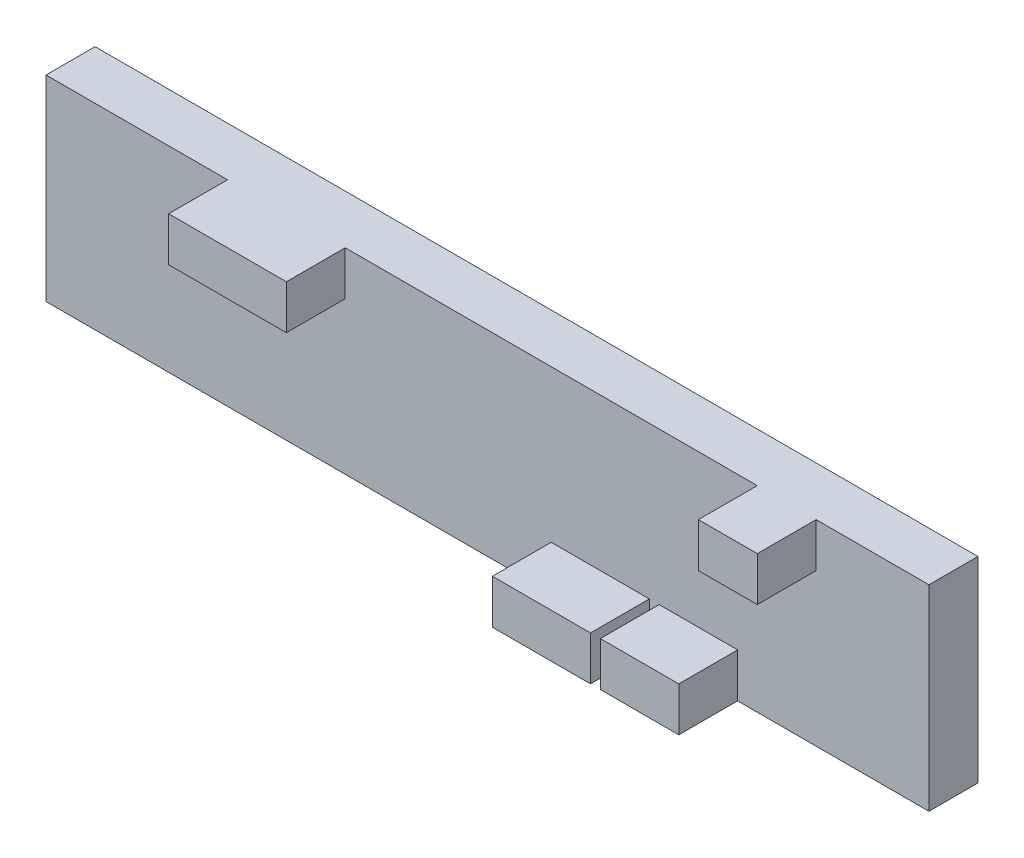
SolidWorks part; units mm, degrees
ref_plane "Спереди" through (0, 0, 0) normal (0, 0, 1) x (1, 0, 0)
ref_plane "Сверху" through (0, 0, 0) normal (0, 1, 0) x (1, 0, 0)
ref_plane "Справа" through (0, 0, 0) normal (1, 0, 0) x (0, 0, -1)
sketch "Эскиз1" plane through (0, 0, 0) normal (0, 0, 1) x (1, 0, 0)
  line L1 (0, 0) -> (91, 0)
  line L2 (0, 0) -> (0, 20)
  line L3 (0, 20) -> (91, 20)
  line L4 (91, 0) -> (91, 20)
extrude "Бобышка-Вытянуть1" add sketch "Эскиз1" along normal blind 5 contours L2 L1 L4 L3
sketch "Эскиз2" plane through (0, 0, 5) normal (0, 0, 1) x (1, 0, 0)
  line L0 (0, 20) -> (91, 20) construction
  line L1 (19, 20) -> (31, 20)
  line L2 (19, 20) -> (19, 15.5)
  line L3 (19, 15.5) -> (31, 15.5)
  line L4 (31, 20) -> (31, 15.5)
  line L5 (0, 0) -> (0, 20) construction
  line L6 (91, 0) -> (91, 20) construction
  line L7 (73, 20) -> (79, 20)
  line L8 (73, 20) -> (73, 15.5)
  line L9 (73, 15.5) -> (79, 15.5)
  line L10 (79, 20) -> (79, 15.5)
  line L20 (0, 0) -> (91, 0) construction
  line L21 (52, 0) -> (62, 0)
  line L22 (52, 0) -> (52, 4.5)
  line L23 (52, 4.5) -> (62, 4.5)
  line L24 (62, 0) -> (62, 4.5)
  line L26 (63, 0) -> (71, 0)
  line L27 (63, 0) -> (63, 4.5)
  line L28 (63, 4.5) -> (71, 4.5)
  line L29 (71, 0) -> (71, 4.5)
  dimension "D1" = 19
  dimension "D2" = 12
  dimension "D3" = 20
  dimension "D4" = 1
  dimension "D5" = 8
extrude "Бобышка-Вытянуть2" add sketch "Эскиз2" along normal blind 6
sketch "Эскиз3" plane through (91, 0, 0) normal (1, 0, 0) x (0, 0, -1)
  line L1 (-5, 20) -> (0, 20)
  line L2 (-5, 20) -> (-5, 0)
  line L3 (-5, 0) -> (0, 0)
  line L4 (0, 20) -> (0, 0)
extrude "Вырез-Вытянуть1" cut sketch "Эскиз3" against normal blind 0.5
sketch "Эскиз4" plane through (0, 0, 0) normal (-1, 0, 0) x (0, 0, 1)
  line L1 (0, 20) -> (5, 20)
  line L2 (0, 20) -> (0, 0)
  line L3 (0, 0) -> (5, 0)
  line L4 (5, 20) -> (5, 0)
extrude "Вырез-Вытянуть2" cut sketch "Эскиз4" against normal blind 0.5
